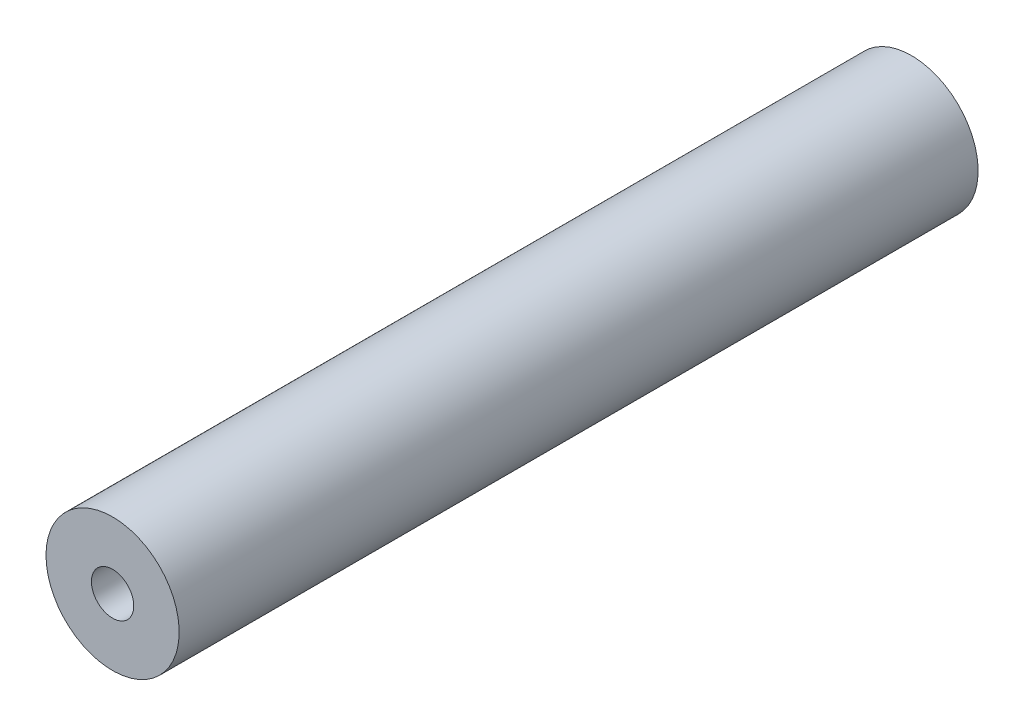
SolidWorks part; units mm, degrees
material "6061-T6 (SS)"
ref_plane "Front Plane" through (0, 0, 0) normal (0, 0, 1) x (1, 0, 0)
ref_plane "Top Plane" through (0, 0, 0) normal (0, 1, 0) x (1, 0, 0)
ref_plane "Right Plane" through (0, 0, 0) normal (1, 0, 0) x (0, 0, -1)
sketch "Sketch1" plane through (0, 0, 0) normal (0, 0, 1) x (1, 0, 0)
  circle A1 centre (0, 0) radius 6.35
  dimension "D2" = 12.7
extrude "Boss-Extrude1" add sketch "Sketch1" along normal mid plane 76.2 contours A1 region at (0, 0, 0)
hole_wizard "#10-32 Tapped Hole1" positions "3DSketch1" profile "Sketch2" tap size "#10-32" standard "ANSI Inch"
sketch3d "3DSketch1"
  line L0 (0, 0, 38.1) -> (0, 0, -38.1) construction
  point P0 (0, 0, -38.1)
  point P4 (0, 0, 38.1)
sketch "Sketch2" plane through (0, 0, -38.1) normal (1, 0, 0) x (0, 1, 0)
  line L0 (0, 0) -> (0, 13.2428)
  line L1 (0, 13.2428) -> (2.0193, 12.0294)
  line L2 (2.0193, 12.0294) -> (2.0193, 0)
  line L5 (2.0193, 0) -> (0, 0)
  line L10 (0, 13.2428) -> (-2.0193, 12.0294) construction
  line L11 (0, -6.35) -> (0, 107.95) construction
  dimension "Tap Drill Dia." = 4.0386
  dimension "Tap Drill Depth" = 12.0294
  dimension "Drill Angle" = 118
cosmetic thread "Hole Thread1"
cosmetic thread "Hole Thread2"
